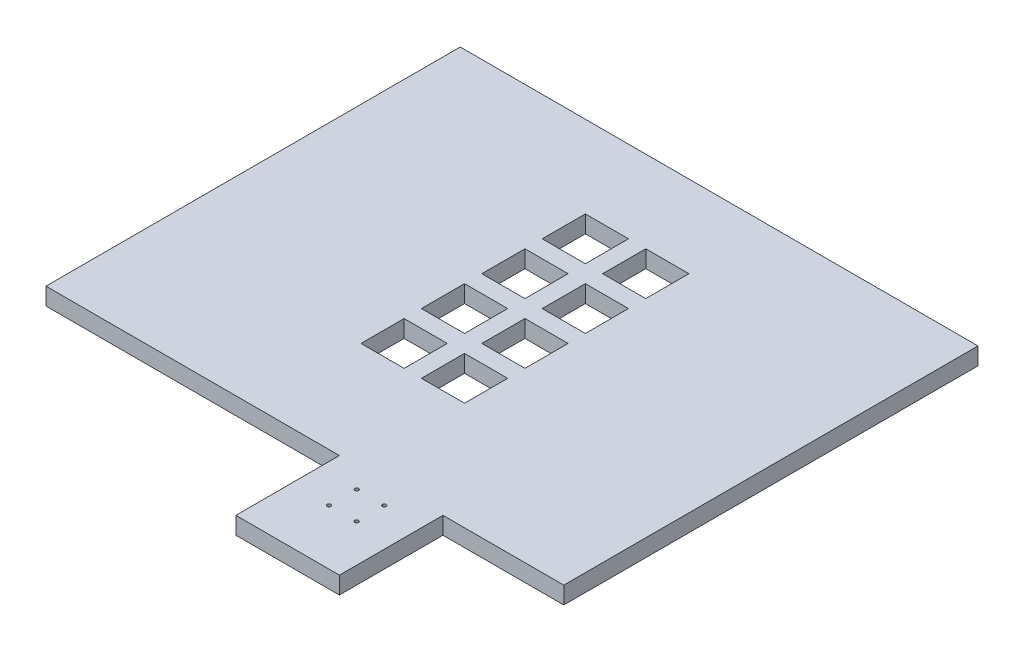
SolidWorks part; units mm, degrees
ref_plane "前基準面" through (0, 0, 0) normal (0, 0, 1) x (1, 0, 0)
ref_plane "上基準面" through (0, 0, 0) normal (0, 1, 0) x (1, 0, 0)
ref_plane "右基準面" through (0, 0, 0) normal (1, 0, 0) x (0, 0, -1)
sketch "草圖1" plane through (0, 0, 0) normal (0, 1, 0) x (1, 0, 0)
  line L0 (50, -1010.2) -> (50, 48989.8) construction
  line L1 (-150, -120) -> (20, -120)
  line L2 (-150, -120) -> (-150, 120)
  line L3 (-150, 120) -> (150, 120)
  line L4 (150, -120) -> (150, 120)
  line L5 (-150, -120) -> (150, 120) construction
  line L6 (-150, 120) -> (150, -120) construction
  line L7 (20, -120) -> (20, -180)
  line L8 (20, -180) -> (80, -180)
  line L9 (80, -180) -> (80, -120)
  line L10 (80, -120) -> (150, -120)
  point P0 (0, 0)
  point P10 (50, -180)
  dimension "D1" = 300
  dimension "D2" = 240
  dimension "D3" = 200
  dimension "D4" = 60
  dimension "D5" = 60
extrude "填料-伸長1" add sketch "草圖1" along normal blind 10
sketch "草圖2" plane through (0, 0, 0) normal (0, -1, 0) x (1, 0, 0)
  line L0 (-980, 140) -> (49020, 140) construction
  line L2 (50, -820) -> (50, 49180) construction
  line L3 (20, 180) -> (80, 180) construction
  line L4 (-150, 120) -> (20, 120) construction
  line L6 (62.5, 152.5) -> (37.5, 152.5)
  line L7 (62.5, 152.5) -> (62.5, 127.5)
  line L8 (62.5, 127.5) -> (37.5, 127.5)
  line L9 (37.5, 152.5) -> (37.5, 127.5)
  line L10 (62.5, 152.5) -> (37.5, 127.5) construction
  line L11 (62.5, 127.5) -> (37.5, 152.5) construction
  circle A0 centre (42, 132) radius 1.1
  circle A1 centre (42, 148) radius 1.1
  circle A2 centre (58, 132) radius 1.1
  circle A3 centre (58, 148) radius 1.1
  point P7 (50, 180)
  point P17 (50, 140)
  dimension "D4" = 2.2
  dimension "D1" = 20
  dimension "D2" = 8
  dimension "D3" = 8
  dimension "D5" = 25
  dimension "D6" = 25
extrude "除料-伸長1" cut sketch "草圖2" against normal blind 8 contours L6 L9 L8 L7 A3 A1 A0 A2 region at (50, 0, 140)
extrude "除料-伸長2" cut sketch "草圖2<3>" against normal through all contours A2 | A0 | A1 | A3
sketch "草圖2<3>" plane through (0, 0, 0) normal (0, -1, 0) x (1, 0, 0) same geometry as "草圖2"
sketch "草圖3" plane through (0, 10, 0) normal (0, 1, 0) x (1, 0, 0)
  line L0 (50, -1180) -> (50, 48820) construction
  line L1 (20, -180) -> (80, -180) construction
  line L2 (0, -1006.6936) -> (0, 48993.3064) construction
  line L3 (-150, 120) -> (-150, -120) construction
  line L4 (-30, 37.5) -> (-5, 37.5)
  line L5 (-30, 37.5) -> (-30, 12.5)
  line L10 (-30, -32.5) -> (-5, -57.5) construction
  line L11 (150, 120) -> (-150, 120) construction
  line L17 (-30, -32.5) -> (-5, -32.5)
  line L22 (-30, 72.5) -> (-5, 72.5)
  line L23 (-30, 72.5) -> (-30, 47.5)
  line L28 (-30, 47.5) -> (-5, 47.5)
  line L29 (-5, 72.5) -> (-5, 47.5)
  line L30 (-30, 12.5) -> (-5, 12.5)
  line L31 (-5, 37.5) -> (-5, 12.5)
  line L36 (-30, 2.5) -> (-5, 2.5)
  line L37 (-30, 2.5) -> (-30, -22.5)
  line L38 (-30, -22.5) -> (-5, -22.5)
  line L39 (-5, 2.5) -> (-5, -22.5)
  line L40 (-30, -32.5) -> (-30, -57.5)
  line L41 (-30, -57.5) -> (-5, -57.5)
  line L42 (-5, -32.5) -> (-5, -57.5)
  line L46 (-30, -57.5) -> (-5, -32.5) construction
  line L47 (-150, -120) -> (20, -120) construction
  line L48 (-30, 72.5) -> (-5, 47.5) construction
  line L50 (-30, 47.5) -> (-5, 72.5) construction
  line L53 (30, -57.5) -> (5, -57.5)
  line L54 (5, -32.5) -> (5, -57.5)
  line L55 (30, -32.5) -> (5, -32.5)
  line L56 (30, -32.5) -> (30, -57.5)
  line L57 (30, 2.5) -> (30, -22.5)
  line L58 (30, -22.5) -> (5, -22.5)
  line L59 (5, 2.5) -> (5, -22.5)
  line L60 (30, 2.5) -> (5, 2.5)
  line L61 (30, 37.5) -> (30, 12.5)
  line L62 (30, 12.5) -> (5, 12.5)
  line L63 (5, 37.5) -> (5, 12.5)
  line L64 (30, 37.5) -> (5, 37.5)
  line L65 (30, 47.5) -> (5, 47.5)
  line L66 (5, 72.5) -> (5, 47.5)
  line L67 (30, 72.5) -> (5, 72.5)
  line L68 (30, 72.5) -> (30, 47.5)
  point P5 (50, -180)
  point P9 (-17.5, -45)
  point P17 (-17.5, 60)
  dimension "D2" = 25
  dimension "D3" = 75
  dimension "D4" = 25
  dimension "D5" = 120
  dimension "D6" = 10
  dimension "D7" = 25
  dimension "D8" = 25
  dimension "D9" = 25
  dimension "D10" = 10
  dimension "D11" = 10
  dimension "D12" = 5
  dimension "D13" = 25
  dimension "D14" = 25
  dimension "D15" = 60
extrude "除料-伸長3" cut sketch "草圖3" against normal through all
fillet "圓角2" radius 2 4 edges at (37.5, 4, 152.5) (62.5, 4, 127.5) (62.5, 4, 152.5) (37.5, 4, 127.5)
